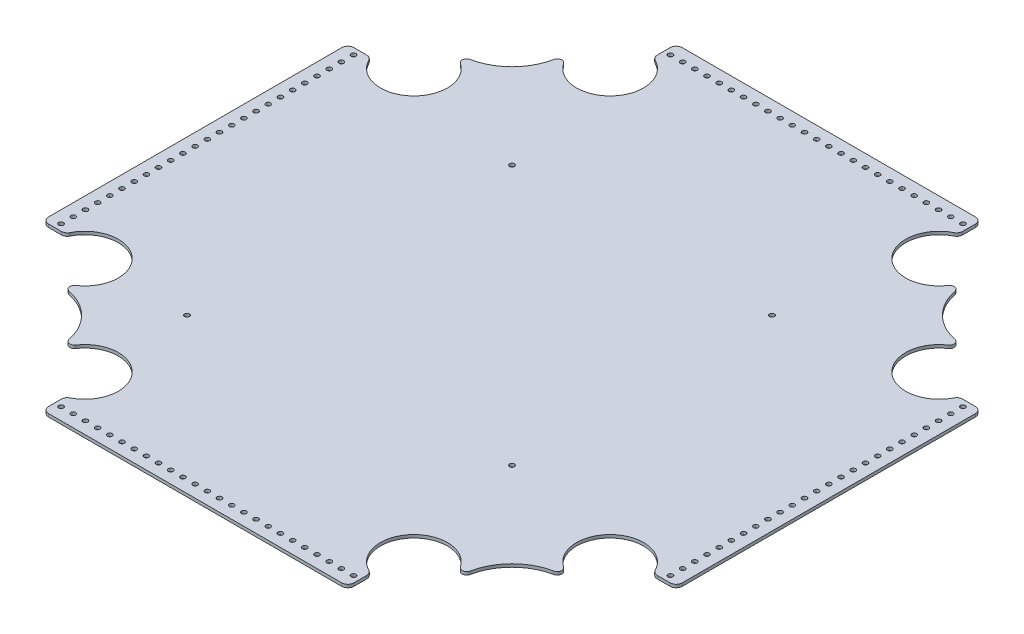
SolidWorks part; units mm, degrees
material "PC High Viscosity"
ref_plane "Front Plane" through (0, 0, 0) normal (0, 0, 1) x (1, 0, 0)
ref_plane "Top Plane" through (0, 0, 0) normal (0, 1, 0) x (1, 0, 0)
ref_plane "Right Plane" through (0, 0, 0) normal (1, 0, 0) x (0, 0, -1)
sketch "Sketch1" plane through (0, 0, 0) normal (0, 1, 0) x (1, 0, 0)
  line L1 (330.2, 330.2) -> (-330.2, 330.2)
  line L2 (330.2, 330.2) -> (330.2, -330.2)
  line L3 (330.2, -330.2) -> (-330.2, -330.2)
  line L4 (-330.2, 330.2) -> (-330.2, -330.2)
  line L5 (330.2, 330.2) -> (-330.2, -330.2) construction
  line L6 (330.2, -330.2) -> (-330.2, 330.2) construction
  point P0 (0, 0)
  dimension "D1" = 660.4
extrude "Boss-Extrude1" add sketch "Sketch1" along normal mid plane 3.175
sketch "Sketch2" plane through (0, 1.5875, 0) normal (0, 1, 0) x (1, 0, 0)
  line L0 (-330.2, -330.2) -> (330.2, -330.2) construction
  line L1 (-330.2, 330.2) -> (-330.2, -330.2) construction
  circle A0 centre (-317.5, -317.5) radius 2.4892
  dimension "D1" = 4.9784
  dimension "D2" = 12.7
  dimension "D3" = 12.7
extrude "Cut-Extrude1" cut sketch "Sketch2" against normal through all
pattern_linear "LPattern1" count 51 spacing 12.7 along (0, 0, -1) count 51 spacing 12.7 along (1, 0, 0) of "Cut-Extrude1" pattern seed only yes
pattern_linear "LPattern2" count 51 spacing 12.7 along (0, 0, -1) of face at (317.5, -1.5875, 319.9892)
pattern_linear "LPattern3" count 50 spacing 12.7 along (1, 0, 0) of face at (-317.5, -1.5875, -315.0108)
sketch "Sketch4" plane through (0, -1.5875, 0) normal (0, -1, 0) x (-1, 0, 0)
  line L0 (-330.2, 159.131) -> (-306.3652, 159.131)
  line L1 (-330.2, -330.2) -> (-330.2, 330.2) construction
  line L2 (-320.675, 160.7185) -> (-314.325, 160.7185) construction
  line L3 (-159.131, 330.2) -> (-159.131, 306.3652)
  line L4 (-330.2, 330.2) -> (330.2, 330.2) construction
  line L5 (-159.131, 330.2) -> (-330.2, 330.2)
  line L6 (-330.2, 330.2) -> (-330.2, 159.131)
  circle A0 centre (-263.525, 263.525) radius 55.5625
  arc A1 (-232.9401, 309.912) -> (-319.0875, 263.525) centre (-263.525, 263.525) ccw construction
  circle A2 centre (-171.45, 273.685) radius 34.925
  circle A3 centre (-273.685, 171.45) radius 34.925
  arc A4 (-140.716, 273.685) -> (-171.45, 304.419) centre (-171.45, 273.685) ccw construction
  arc A5 (-304.8, 171.45) -> (-251.6834, 149.4484) centre (-273.685, 171.45) ccw construction
  arc A6 (-254.2153, 200.4446) -> (-252.5049, 209.0663) centre (-251.5604, 204.3984) cw
  arc A7 (-209.0663, 252.5049) -> (-200.4446, 254.2153) centre (-204.3984, 251.5604) cw
  dimension "D1" = 69.85
  dimension "D2" = 1.5875
  dimension "D3" = 4.7625
extrude "Cut-Extrude2" cut sketch "Sketch4" against normal through all contours A0 A7 A2 L3 L5 L6 L0 A3 A6 | A0 | A3 | A2 region at (327.7807, -1.5875, -244.6655) region at (273.685, -1.5875, -171.45) region at (263.525, -1.5875, -263.525) region at (171.45, -1.5875, -273.685)
mirror "Mirror2" about plane through (0, 0, 0) normal (1, 0, 0) of "Cut-Extrude2"
mirror "Mirror3" about plane through (0, 0, 0) normal (0, 0, 1) of "Cut-Extrude2", "Mirror2"
fillet "Fillet1" radius 6.35 16 edges at (-330.2, 0, -159.131) (-306.3652, 0, -159.131) (-159.131, 0, -306.3652) (-159.131, 0, -330.2) (159.131, 0, -330.2) (159.131, 0, -306.3652) (306.3652, 0, -159.131) (330.2, 0, -159.131) (330.2, 0, 159.131) (306.3652, 0, 159.131) (159.131, 0, 306.3652) (159.131, 0, 330.2) (-159.131, 0, 330.2) (-159.131, 0, 306.3652) (-330.2, 0, 159.131) (-306.3652, 0, 159.131)
sketch "Sketch5" plane through (0, -1.5875, 0) normal (0, -1, 0) x (1, 0, 0)
  circle A0 centre (135.4667, 135.4667) radius 2.4892 construction
  circle A1 centre (135.4667, -135.4667) radius 2.4892 construction
  circle A2 centre (-135.4667, -135.4667) radius 2.4892 construction
  circle A3 centre (-169.3333, 169.3333) radius 2.4892 construction
  circle A4 centre (135.4667, 135.4667) radius 2.4892
  circle A5 centre (135.4667, -135.4667) radius 2.4892
  circle A6 centre (-135.4667, -135.4667) radius 2.4892
  circle A8 centre (-169.3333, 169.3333) radius 2.4892
  point P7 (0, 0)
extrude "Cut-Extrude3" cut sketch "Sketch5" against normal through all
